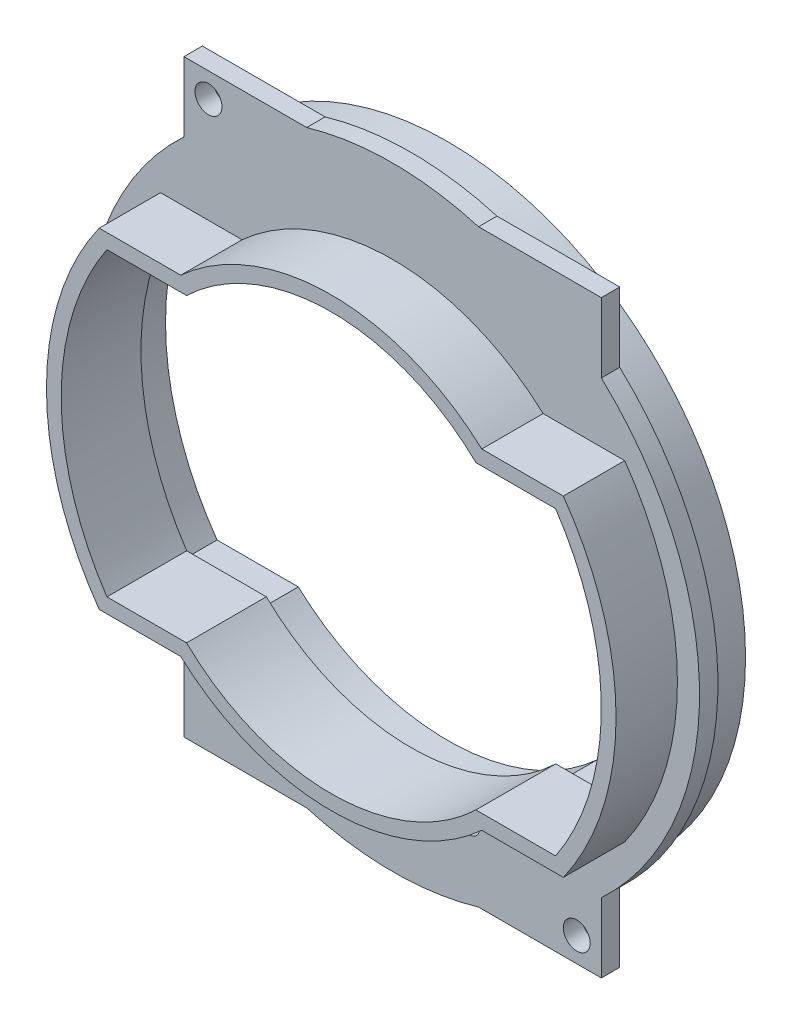
SolidWorks part; units mm, degrees
ref_plane "前视基准面" through (0, 0, 0) normal (0, 0, 1) x (1, 0, 0)
ref_plane "上视基准面" through (0, 0, 0) normal (0, 1, 0) x (1, 0, 0)
ref_plane "右视基准面" through (0, 0, 0) normal (1, 0, 0) x (0, 0, -1)
other "Configuration Table"
sketch "草图1" plane through (0, 0, 0) normal (0, 0, 1) x (1, 0, 0)
  line L0 (18.274, 12.25) -> (-18.274, 12.25)
  line L1 (-18.274, -12.25) -> (18.274, -12.25)
  line L2 (-26.9084, 0) -> (29.3247, 0) construction
  circle A0 centre (0, 0) radius 17
  circle A1 centre (0, 0) radius 22
  circle A2 centre (0, 0) radius 25
  dimension "D1" = 34
  dimension "D2" = 44
  dimension "D4" = 50
  dimension "D3" = 24.5
extrude "凸台-拉伸1" add sketch "草图1" along normal blind 1.5 contours A2 L2 A1 | L2 A2 A1 | L1 A1 A0 | L0 A1 A0 region at (0, 22.559, 0) region at (0, 17.1494, 0) region at (23.5, -0.559, 0) region at (0, -17.1494, 0)
sketch "草图2" plane through (0, 0, 1.5) normal (0, 0, 1) x (1, 0, 0)
  line L0 (-18.274, 12.25) -> (-11.7872, 12.25)
  line L1 (11.7872, 12.25) -> (18.274, 12.25)
  line L2 (11.7872, -12.25) -> (18.274, -12.25)
  line L3 (-18.274, -12.25) -> (-11.7872, -12.25)
  line L4 (-18.9034, 13.45) -> (-12.2612, 13.45)
  line L5 (12.2612, 13.45) -> (18.9034, 13.45)
  line L6 (12.2612, -13.45) -> (18.9034, -13.45)
  line L7 (-18.9034, -13.45) -> (-12.2612, -13.45)
  arc A0 (18.274, 12.25) -> (18.274, -12.25) centre (0, 0) cw
  arc A1 (11.7872, -12.25) -> (-11.7872, -12.25) centre (0, 0) cw
  arc A2 (-11.7872, 12.25) -> (11.7872, 12.25) centre (0, 0) cw
  arc A3 (-18.274, -12.25) -> (-18.274, 12.25) centre (0, 0) cw
  arc A4 (-12.2612, 13.45) -> (12.2612, 13.45) centre (0, 0) cw
  arc A5 (18.9034, 13.45) -> (18.9034, -13.45) centre (0, 0) cw
  arc A6 (12.2612, -13.45) -> (-12.2612, -13.45) centre (0, 0) cw
  arc A7 (-18.9034, -13.45) -> (-18.9034, 13.45) centre (0, 0) cw
  dimension "D1" = 1.2
extrude "凸台-拉伸2" add sketch "草图2" along normal blind 5
sketch "草图5" plane through (0, 0, 0) normal (0, 0, -1) x (-1, 0, 0)
  line L40 (-18.7999, -13.25) -> (-12.1835, -13.25)
  line L41 (12.1835, -13.25) -> (18.7999, -13.25)
  line L42 (18.7999, 13.25) -> (12.1835, 13.25)
  line L43 (-12.1835, 13.25) -> (-18.7999, 13.25)
  line L44 (-18.7999, -13.25) -> (-12.1835, -13.25)
  line L45 (12.1835, -13.25) -> (18.7999, -13.25)
  line L46 (18.7999, 13.25) -> (12.1835, 13.25)
  line L47 (-12.1835, 13.25) -> (-18.7999, 13.25)
  circle A37 centre (0, 0) radius 24.25
  arc A41 (-18.7999, 13.25) -> (-18.7999, -13.25) centre (0, 0) ccw
  arc A42 (-12.1835, -13.25) -> (12.1835, -13.25) centre (0, 0) ccw
  arc A43 (18.7999, -13.25) -> (18.7999, 13.25) centre (0, 0) ccw
  arc A44 (12.1835, 13.25) -> (-12.1835, 13.25) centre (0, 0) ccw
  arc A45 (-18.7999, 13.25) -> (-18.7999, -13.25) centre (0, 0) ccw
  arc A46 (-12.1835, -13.25) -> (12.1835, -13.25) centre (0, 0) ccw
  arc A47 (18.7999, -13.25) -> (18.7999, 13.25) centre (0, 0) ccw
  arc A48 (12.1835, 13.25) -> (-12.1835, 13.25) centre (0, 0) ccw
  dimension "D2" = 48.5
  dimension "D1" = 1
extrude "凸台-拉伸4" add sketch "草图5" along normal blind 3
sketch "草图6" plane through (0, 0, 0) normal (0, 0, 1) x (1, 0, 0)
  line L1 (-17, -24) -> (17, -24)
  line L2 (-17, -24) -> (-17, 24)
  line L3 (-17, 24) -> (17, 24)
  line L4 (17, -24) -> (17, 24)
  line L5 (-17, -24) -> (17, 24) construction
  line L6 (-17, 24) -> (17, -24) construction
  circle A2 centre (0, 0) radius 24
  point P0 (0, 0)
  dimension "D1" = 34
  dimension "D2" = 48
extrude "凸台-拉伸5" add sketch "草图6" along normal blind 1.5 contours A2 L3 L2 | A2 L4 L3 | A2 L1 L4 | A2 L2 L1 region at (-12.8852, -21.949, 0) region at (12.8852, -21.949, 0) region at (-12.8852, 21.949, 0) region at (12.8852, 21.949, 0)
sketch "草图7" plane through (0, 0, -3) normal (0, 0, -1) x (-1, 0, 0)
  line L0 (-12.8572, -14.6609) -> (0, 0) construction
  line L1 (0, 0) -> (0, -19.5) construction
  line L2 (0, 0) -> (-12.8572, -14.6609) construction
  line L3 (0, 0) -> (-10.8336, -16.2137) construction
  circle A0 centre (0, 0) radius 19.5 construction
  circle A1 centre (-12.8572, -14.6609) radius 0.5
  circle A2 centre (-10.8336, -16.2137) radius 0.5
  circle A3 centre (-8.6246, -17.489) radius 0.5
  circle A4 centre (-6.2681, -18.4651) radius 0.5
  circle A5 centre (-3.8043, -19.1253) radius 0.5
  circle A6 centre (-1.2754, -19.4582) radius 0.5
  circle A7 centre (1.2754, -19.4582) radius 0.5
  circle A8 centre (3.8043, -19.1253) radius 0.5
  circle A9 centre (6.2681, -18.4651) radius 0.5
  circle A10 centre (8.6246, -17.489) radius 0.5
  dimension "D1" = 39
  dimension "D2" = 1
  dimension "D3" = 41.25
  dimension "D5" = 7.5
  dimension "D4" = 10
extrude "切除-拉伸2" cut sketch "草图7" against normal through all
sketch "草图8" plane through (0, 0, 1.5) normal (0, 0, 1) x (1, 0, 0)
  line L0 (0, 0) -> (12.8572, -14.6609) construction
  line L1 (0, 0) -> (10.8336, -16.2137) construction
  circle A0 centre (12.8572, -14.6609) radius 0.8
  circle A1 centre (10.8336, -16.2137) radius 0.8
  circle A2 centre (8.6246, -17.489) radius 0.8
  circle A3 centre (6.2681, -18.4651) radius 0.8
  circle A4 centre (3.8043, -19.1253) radius 0.8
  circle A5 centre (1.2754, -19.4582) radius 0.8
  circle A6 centre (-1.2754, -19.4582) radius 0.8
  circle A7 centre (-3.8043, -19.1253) radius 0.8
  circle A8 centre (-6.2681, -18.4651) radius 0.8
  circle A9 centre (-8.6246, -17.489) radius 0.8
  dimension "D1" = 1.6
  dimension "D3" = 7.5
  dimension "D2" = 10
extrude "切除-拉伸3" cut sketch "草图8" against normal blind 3.5
sketch "草图9" plane through (0, 0, 1.5) normal (0, 0, 1) x (1, 0, 0)
  line L0 (-17, 24) -> (-7, 24) construction
  line L1 (-17, 18.3303) -> (-17, 24) construction
  line L2 (17, -24) -> (17, -18.3303) construction
  line L3 (7, -24) -> (17, -24) construction
  circle A0 centre (-15, 22) radius 1.1
  circle A1 centre (15, -22) radius 1.1
  point P12 (15.8317, -23.8056)
  dimension "D1" = 2.2
  dimension "D2" = 2
  dimension "D3" = 2
  dimension "D4" = 2
  dimension "D5" = 2
extrude "切除-拉伸4" cut sketch "草图9" against normal blind 10
